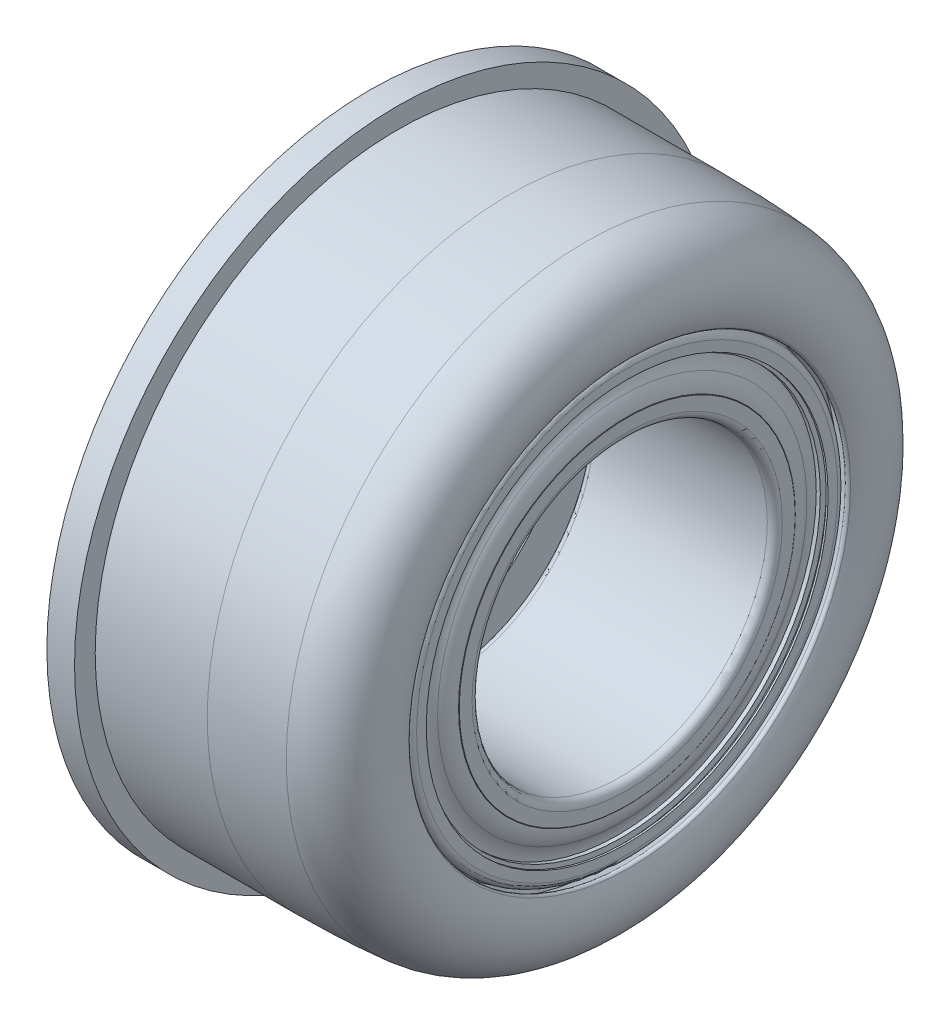
SolidWorks part; units mm, degrees
ref_plane "Front Plane" through (0, 0, 0) normal (0, 0, 1) x (1, 0, 0)
ref_plane "Top Plane" through (0, 0, 0) normal (0, 1, 0) x (1, 0, 0)
ref_plane "Right Plane" through (0, 0, 0) normal (1, 0, 0) x (0, 0, -1)
sketch "External Component" plane through (0, 0, 0) normal (0, 0, 1) x (1, 0, 0)
  line L0 (-3.6, 0) -> (3.6, 0) construction
  line L1 (-3.473, 4.25) -> (-2.723, 4.25) construction
  line L2 (-2.596, 4.377) -> (-2.596, 5.75) construction
  line L3 (3.6, 0) -> (3.6, 8.19) construction
  line L4 (-3.6, 4.377) -> (-3.473, 4.25) construction
  line L5 (1.03, 6.258) -> (1.4896, 7.0541) construction
  line L6 (-2.85, 8.19) -> (-2.85, 8.75) construction
  line L7 (-2.85, 8.75) -> (-3.6, 8.75) construction
  line L8 (-3.6, 8.75) -> (-3.6, 4.377) construction
  line L9 (2.13, 6.6433) -> (3.3318, 5.9494) construction
  line L10 (-2.723, 4.25) -> (-2.596, 4.377) construction
  line L11 (-2.596, 5.75) -> (-2.086, 5.75) construction
  line L12 (-2.086, 5.75) -> (-0.66, 6.1589) construction
  line L13 (-0.66, 6.1589) -> (-0.66, 6.258) construction
  line L14 (-0.66, 6.258) -> (1.03, 6.258) construction
  line L15 (2.13, 6.6433) -> (2.13, 7.4033) construction
  line L16 (2.13, 6.6433) -> (2.89, 6.6433) construction
  line L17 (0.185, 8.19) -> (-2.85, 8.19) construction
  arc A0 (3.4432, 5.9827) -> (2.2458, 8.1087) centre (2.13, 6.6433) ccw construction
  arc A1 (2.7882, 6.2633) -> (2.89, 6.6433) centre (2.13, 6.6433) ccw construction
  arc A2 (3.4432, 5.9827) -> (3.3318, 5.9494) centre (3.3718, 6.0187) cw construction
  arc A3 (2.89, 6.6433) -> (2.13, 7.4033) centre (2.13, 6.6433) ccw construction
  arc A4 (0.185, 8.19) -> (2.2458, 8.1087) centre (0.185, -17.9654) cw construction
  arc A5 (1.4896, 7.0541) -> (2.13, 7.4033) centre (2.0958, 6.7041) cw construction
  point P0 (-3.6, 4.25)
  point P3 (0, 0)
  point P19 (-2.596, 4.25)
  point P29 (0.185, 6.258)
  dimension "D10" = 0.08
  dimension "D11" = 0.76
  dimension "D5" = 0.7
  dimension "D1" = 0.254
  dimension "D2" = 1.5
  dimension "D6" = 0.51
  dimension "D7" = 164
  dimension "D8" = 0.508
  dimension "D9" = 30
  dimension "D13" = 2.94
  dimension "D14" = 1.69
  dimension "D15" = 120
sketch "Internal Component" plane through (0, 0, 0) normal (0, 0, 1) x (1, 0, 0)
  line L0 (3.1239, 5.4442) -> (2.9739, 5.4442)
  line L1 (3.374, 5.7058) -> (3.374, 5.4442)
  line L2 (3.374, 5.4442) -> (3.3232, 5.4442)
  line L3 (3.3232, 5.4442) -> (3.2334, 5.534)
  line L4 (3.2334, 5.534) -> (3.1239, 5.534)
  line L5 (3.1239, 5.534) -> (3.1239, 5.4442)
  line L6 (0.834, 4.2001) -> (0.834, 0) construction
  line L7 (-3.6, 0) -> (3.6, 0) construction
  line L8 (-1.706, 0) -> (3.374, 0) construction
  line L9 (2.9739, 5.4442) -> (2.9739, 5.1902)
  line L10 (-2.086, 5.75) -> (-0.66, 6.1589) construction
  line L11 (2.9739, 5.1902) -> (1.4226, 5.1902)
  line L12 (-1.306, 5.4442) -> (-1.306, 5.1902)
  line L13 (-1.456, 5.534) -> (-1.456, 5.4442)
  line L14 (-1.5654, 5.534) -> (-1.456, 5.534)
  line L15 (-1.6552, 5.4442) -> (-1.5654, 5.534)
  line L16 (-1.706, 5.4442) -> (-1.6552, 5.4442)
  line L17 (-1.706, 5.7058) -> (-1.706, 5.4442)
  line L18 (-1.456, 5.4442) -> (-1.306, 5.4442)
  line L19 (0.2454, 5.1902) -> (-1.306, 5.1902)
  line L20 (1.4226, 4.55) -> (3.1239, 4.55)
  line L22 (-1.706, 4.55) -> (-1.706, 4.2032)
  line L23 (-1.5028, 4) -> (3.1708, 4)
  line L24 (3.374, 4.55) -> (3.374, 4.2032)
  line L25 (3.1239, 4.55) -> (3.1239, 4.47)
  line L26 (3.1239, 4.47) -> (3.2334, 4.47)
  line L27 (3.2334, 4.47) -> (3.2334, 4.55)
  line L28 (3.2334, 4.55) -> (3.374, 4.55)
  line L29 (-1.5654, 4.55) -> (-1.706, 4.55)
  line L30 (-1.5654, 4.47) -> (-1.5654, 4.55)
  line L31 (-1.456, 4.47) -> (-1.5654, 4.47)
  line L32 (-1.456, 4.55) -> (-1.456, 4.47)
  line L33 (0.2454, 4.55) -> (-1.456, 4.55)
  line L34 (0.834, 4.8701) -> (0.164, 4.8701) construction
  line L35 (0.164, 5.1902) -> (0.164, 4.55) construction
  line L36 (-2.596, 4.377) -> (-2.596, 5.75) construction
  arc A0 (-1.5588, 5.9012) -> (3.2268, 5.9012) centre (0.834, -2.4435) cw
  arc A1 (3.2268, 5.9012) -> (3.374, 5.7058) centre (3.1708, 5.7058) cw
  arc A2 (-1.5588, 5.9012) -> (-1.706, 5.7058) centre (-1.5028, 5.7058) ccw
  arc A3 (1.4226, 5.1902) -> (0.2454, 5.1902) centre (0.834, 4.8701) ccw
  arc A4 (1.4226, 5.1902) -> (0.2454, 5.1902) centre (0.834, 4.8701) ccw construction
  arc A5 (0.2454, 4.55) -> (1.4226, 4.55) centre (0.834, 4.8701) ccw
  circle A6 centre (0.834, 4.8701) radius 0.67 construction
  arc A7 (3.374, 4.2032) -> (3.1708, 4) centre (3.1708, 4.2032) cw
  arc A8 (-1.5028, 4) -> (-1.706, 4.2032) centre (-1.5028, 4.2032) cw
  point P2 (3.3486, 5.4442)
  point P16 (0.834, 0)
  point P53 (0.164, 4.8701)
  dimension "D3" = 0.127
  dimension "D6" = 0.2032
  dimension "D12" = 0.2032
  dimension "D15" = 0.67
  dimension "D1" = 0.0508
  dimension "D2" = 135
  dimension "D5" = 5.08
  dimension "D7" = 0.254
  dimension "D8" = 0.15
  dimension "D9" = 0.4001
  dimension "D10" = 0.457
  dimension "D11" = 0.08
  dimension "D13" = 9.1
  dimension "D4" = 0.89
sketch "External Body Sketch" plane through (0, 0, 0) normal (0, 0, 1) x (1, 0, 0)
  line L0 (-2.85, 8.75) -> (-3.6, 8.75) construction
  line L1 (-2.85, 8.19) -> (-2.85, 8.75) construction
  line L2 (0.185, 8.19) -> (-2.85, 8.19) construction
  line L3 (2.13, 6.6433) -> (3.3318, 5.9494) construction
  line L4 (1.03, 6.258) -> (1.4896, 7.0541) construction
  line L5 (-0.66, 6.258) -> (1.03, 6.258) construction
  line L6 (-0.66, 6.1589) -> (-0.66, 6.258) construction
  line L7 (-2.086, 5.75) -> (-0.66, 6.1589) construction
  line L8 (-2.596, 5.75) -> (-2.086, 5.75) construction
  line L9 (-2.596, 4.377) -> (-2.596, 5.75) construction
  line L10 (-2.723, 4.25) -> (-2.596, 4.377) construction
  line L11 (-3.473, 4.25) -> (-2.723, 4.25) construction
  line L12 (-3.6, 4.377) -> (-3.473, 4.25) construction
  line L13 (-3.6, 8.75) -> (-3.6, 4.377) construction
  line L14 (-2.85, 8.75) -> (-3.6, 8.75)
  line L15 (-2.85, 8.19) -> (-2.85, 8.75)
  line L16 (0.185, 8.19) -> (-2.85, 8.19)
  line L17 (2.13, 6.6433) -> (3.3318, 5.9494)
  line L18 (1.03, 6.258) -> (1.4896, 7.0541)
  line L19 (-0.66, 6.258) -> (1.03, 6.258)
  line L20 (-0.66, 6.1589) -> (-0.66, 6.258)
  line L21 (-2.086, 5.75) -> (-0.66, 6.1589)
  line L22 (-2.596, 5.75) -> (-2.086, 5.75)
  line L23 (-2.596, 4.377) -> (-2.596, 5.75)
  line L24 (-2.723, 4.25) -> (-2.596, 4.377)
  line L25 (-3.473, 4.25) -> (-2.723, 4.25)
  line L26 (-3.6, 4.377) -> (-3.473, 4.25)
  line L27 (-3.6, 8.75) -> (-3.6, 4.377)
  arc A0 (2.2458, 8.1087) -> (0.185, 8.19) centre (0.185, -17.9654) ccw construction
  arc A1 (3.4432, 5.9827) -> (2.2458, 8.1087) centre (2.13, 6.6433) ccw construction
  arc A2 (3.3318, 5.9494) -> (3.4432, 5.9827) centre (3.3718, 6.0187) ccw construction
  arc A3 (2.7882, 6.2633) -> (2.89, 6.6433) centre (2.13, 6.6433) ccw construction
  arc A5 (2.2458, 8.1087) -> (0.185, 8.19) centre (0.185, -17.9654) ccw
  arc A6 (3.4432, 5.9827) -> (2.2458, 8.1087) centre (2.13, 6.6433) ccw
  arc A7 (3.3318, 5.9494) -> (3.4432, 5.9827) centre (3.3718, 6.0187) ccw
  arc A8 (2.7882, 6.2633) -> (2.89, 6.6433) centre (2.13, 6.6433) ccw
  arc A9 (2.89, 6.6433) -> (2.13, 7.4033) centre (2.13, 6.6433) ccw construction
  arc A10 (2.13, 7.4033) -> (1.4896, 7.0541) centre (2.0958, 6.7041) ccw construction
  arc A11 (2.89, 6.6433) -> (2.13, 7.4033) centre (2.13, 6.6433) ccw
  arc A12 (2.13, 7.4033) -> (1.4896, 7.0541) centre (2.0958, 6.7041) ccw
revolve "External Component Revolve" add sketch "External Body Sketch" angle 360 about L0 region at (-0.9112, 6.9559, 0)
sketch "Sketch6" plane through (0, 0, 0) normal (0, 0, 1) x (1, 0, 0)
  line L13 (-1.706, 4.55) -> (-1.706, 4.2032)
  line L14 (-1.5654, 4.55) -> (-1.706, 4.55)
  line L15 (-1.5654, 4.47) -> (-1.5654, 4.55)
  line L16 (-1.306, 5.1902) -> (0.2454, 5.1902)
  line L17 (-1.306, 5.4442) -> (-1.306, 5.1902)
  line L18 (-1.456, 5.4442) -> (-1.306, 5.4442)
  line L19 (-1.456, 5.534) -> (-1.456, 5.4442)
  line L20 (-1.5654, 5.534) -> (-1.456, 5.534)
  line L21 (-1.6552, 5.4442) -> (-1.5654, 5.534)
  line L22 (-1.706, 5.4442) -> (-1.6552, 5.4442)
  line L23 (-1.706, 5.7058) -> (-1.706, 5.4442)
  line L24 (3.374, 5.4442) -> (3.374, 5.7058)
  line L25 (3.3232, 5.4442) -> (3.374, 5.4442)
  line L26 (3.2334, 5.534) -> (3.3232, 5.4442)
  line L27 (3.1239, 5.534) -> (3.2334, 5.534)
  line L28 (3.1239, 5.4442) -> (3.1239, 5.534)
  line L29 (2.9739, 5.4442) -> (3.1239, 5.4442)
  line L30 (2.9739, 5.1902) -> (2.9739, 5.4442)
  line L31 (1.4226, 5.1902) -> (2.9739, 5.1902)
  line L32 (-1.306, 5.1902) -> (0.2454, 5.1902)
  line L33 (-1.306, 5.4442) -> (-1.306, 5.1902)
  line L34 (-1.456, 5.4442) -> (-1.306, 5.4442)
  line L35 (-1.456, 5.534) -> (-1.456, 5.4442)
  line L36 (-1.5654, 5.534) -> (-1.456, 5.534)
  line L37 (-1.6552, 5.4442) -> (-1.5654, 5.534)
  line L38 (-1.706, 5.4442) -> (-1.6552, 5.4442)
  line L39 (-1.706, 5.7058) -> (-1.706, 5.4442)
  line L40 (3.374, 5.4442) -> (3.374, 5.7058)
  line L41 (3.3232, 5.4442) -> (3.374, 5.4442)
  line L42 (3.2334, 5.534) -> (3.3232, 5.4442)
  line L43 (3.1239, 5.534) -> (3.2334, 5.534)
  line L44 (3.1239, 5.4442) -> (3.1239, 5.534)
  line L45 (2.9739, 5.4442) -> (3.1239, 5.4442)
  line L46 (2.9739, 5.1902) -> (2.9739, 5.4442)
  line L47 (1.4226, 5.1902) -> (2.9739, 5.1902)
  line L48 (-1.456, 4.47) -> (-1.5654, 4.47)
  line L49 (-1.456, 4.55) -> (-1.456, 4.47)
  line L50 (0.2454, 4.55) -> (-1.456, 4.55)
  line L51 (3.1239, 4.55) -> (1.4226, 4.55)
  line L52 (3.1239, 4.47) -> (3.1239, 4.55)
  line L53 (3.2334, 4.47) -> (3.1239, 4.47)
  line L54 (3.2334, 4.55) -> (3.2334, 4.47)
  line L55 (3.374, 4.55) -> (3.2334, 4.55)
  line L56 (3.374, 4.2032) -> (3.374, 4.55)
  line L57 (-1.5028, 4) -> (3.1708, 4)
  line L58 (-1.706, 4.55) -> (-1.706, 4.2032)
  line L59 (-1.5654, 4.55) -> (-1.706, 4.55)
  line L60 (-1.5654, 4.47) -> (-1.5654, 4.55)
  line L61 (-1.456, 4.47) -> (-1.5654, 4.47)
  line L62 (-1.456, 4.55) -> (-1.456, 4.47)
  line L63 (0.2454, 4.55) -> (-1.456, 4.55)
  line L64 (3.1239, 4.55) -> (1.4226, 4.55)
  line L65 (3.1239, 4.47) -> (3.1239, 4.55)
  line L66 (3.2334, 4.47) -> (3.1239, 4.47)
  line L67 (3.2334, 4.55) -> (3.2334, 4.47)
  line L68 (3.374, 4.55) -> (3.2334, 4.55)
  line L69 (3.374, 4.2032) -> (3.374, 4.55)
  line L70 (-1.5028, 4) -> (3.1708, 4)
  arc A3 (0.2454, 4.55) -> (1.4226, 4.55) centre (0.834, 4.8701) ccw
  arc A4 (1.4226, 5.1902) -> (0.2454, 5.1902) centre (0.834, 4.8701) ccw
  arc A5 (-1.5588, 5.9012) -> (-1.706, 5.7058) centre (-1.5028, 5.7058) ccw
  arc A6 (3.2268, 5.9012) -> (-1.5588, 5.9012) centre (0.834, -2.4435) ccw
  arc A7 (3.374, 5.7058) -> (3.2268, 5.9012) centre (3.1708, 5.7058) ccw
  arc A8 (1.4226, 5.1902) -> (0.2454, 5.1902) centre (0.834, 4.8701) ccw
  arc A9 (-1.5588, 5.9012) -> (-1.706, 5.7058) centre (-1.5028, 5.7058) ccw
  arc A10 (3.2268, 5.9012) -> (-1.5588, 5.9012) centre (0.834, -2.4435) ccw
  arc A11 (3.374, 5.7058) -> (3.2268, 5.9012) centre (3.1708, 5.7058) ccw
  arc A12 (3.1708, 4) -> (3.374, 4.2032) centre (3.1708, 4.2032) ccw
  arc A13 (-1.706, 4.2032) -> (-1.5028, 4) centre (-1.5028, 4.2032) ccw
  arc A14 (0.2454, 4.55) -> (1.4226, 4.55) centre (0.834, 4.8701) ccw
  arc A15 (3.1708, 4) -> (3.374, 4.2032) centre (3.1708, 4.2032) ccw
  arc A16 (-1.706, 4.2032) -> (-1.5028, 4) centre (-1.5028, 4.2032) ccw
  dimension "D1" = 0
  dimension "D2" = 0
revolve "Internal Component Revolve" add sketch "Sketch6" angle 360 about L0
sketch "O-Ring Sketch" plane through (0, 0, 0) normal (0, 0, 1) x (1, 0, 0)
  circle A2 centre (2.13, 6.6433) radius 0.76
  arc A3 (2.89, 6.6433) -> (2.13, 7.4033) centre (2.13, 6.6433) ccw construction
revolve "O-Ring" add sketch "O-Ring Sketch" angle 360 about L0
sketch "Sketch7" plane through (0, 0, 0) normal (0, 0, 1) x (1, 0, 0)
  line L1 (-0.309, 5.1749) -> (1.977, 5.1749)
  line L2 (-0.309, 5.1749) -> (-0.309, 4.5653)
  line L3 (-0.309, 4.5653) -> (1.977, 4.5653)
  line L4 (1.977, 5.1749) -> (1.977, 4.5653)
  line L5 (-0.309, 5.1749) -> (1.977, 4.5653) construction
  line L6 (1.977, 5.1749) -> (-0.309, 4.5653) construction
  dimension "D1" = 2.286
  dimension "D2" = 0.6096
revolve "Middle Ring" add sketch "Sketch7" angle 360 about L0
sketch "Sketch8" plane through (0, 0, 0) normal (0, 0, 1) x (1, 0, 0)
  line L0 (0.834, 5.5401) -> (0.834, 4.2001) construction
  line L1 (0.834, 5.5401) -> (0.834, 4.2001)
  circle A0 centre (0.834, 4.8701) radius 0.67 construction
  arc A1 (0.834, 4.2001) -> (0.834, 5.5401) centre (0.834, 4.8701) ccw
revolve "Rollerball" add sketch "Sketch8" angle 360 about L0
sketch "Sketch10" plane through (0, 0, 0) normal (0, 1, 0) x (1, 0, 0)
  line L0 (-3.6, 0) -> (3.6, 0) construction
  line L1 (0.834, 0.67) -> (-3.6, 0.67)
  line L2 (-3.6, 0.67) -> (-3.6, -0.67)
  line L3 (-3.6, -0.67) -> (0.834, -0.67)
  arc A0 (0.834, -0.67) -> (0.834, 0.67) centre (0.834, 0) ccw
  dimension "D1" = 0.67
extrude "Middle Ring Cut" cut sketch "Sketch10" along normal through all
pattern_circular "Cut Circle Pattern" count 10 over 360 about axis through (-3.6, 0, 0) along (-1, 0, 0) of "Middle Ring Cut" reverse direction yes
pattern_circular "Rollerball Cirlce Pattern" count 10 over 360 about axis through (-3.6, 0, 0) along (-1, 0, 0) of bodies 109
sketch "Sketch11" plane through (0, 0, 0) normal (0, 0, 1) x (1, 0, 0)
  line L0 (0.834, 0) -> (0.834, 4.2001) construction
  line L1 (3.1787, 5.534) -> (3.1787, 4.47) construction
  line L2 (3.2334, 5.534) -> (3.1239, 5.534) construction
  line L3 (3.1239, 4.47) -> (3.2334, 4.47) construction
  line L4 (3.1787, 5.002) -> (0.834, 5.002) construction
  line L5 (3.2334, 5.534) -> (3.2334, -5.534) construction
  line L6 (3.1239, 5.534) -> (3.2334, 5.534)
  line L7 (3.1239, 5.534) -> (3.1239, 5.374)
  line L8 (3.1239, 5.374) -> (3.2334, 5.374)
  line L9 (3.2334, 5.534) -> (3.2334, 5.374)
  line L10 (2.9854, 5.4315) -> (3.1124, 5.4315)
  line L11 (3.2402, 4.5627) -> (3.3672, 4.5627)
  line L12 (3.3037, 4.55) -> (3.3037, 4.5627) construction
  line L13 (3.2334, 4.55) -> (3.374, 4.55) construction
  line L14 (3.0489, 5.4315) -> (3.0489, 5.4442) construction
  line L15 (3.1239, 5.4442) -> (2.9739, 5.4442) construction
  line L16 (3.1129, 5.002) -> (3.2399, 5.002) construction
  line L17 (-3.6, 0) -> (3.6, 0) construction
  line L18 (-3.6, 0) -> (3.6, 0) construction
  line L19 (-1.456, 5.374) -> (-1.5654, 5.374)
  line L20 (-1.5654, 5.534) -> (-1.5654, 5.374)
  line L21 (-1.456, 5.534) -> (-1.5654, 5.534)
  line L22 (-1.456, 5.534) -> (-1.456, 5.374)
  line L23 (-1.3175, 5.4315) -> (-1.4445, 5.4315)
  line L24 (-1.5722, 4.5627) -> (-1.6992, 4.5627)
  line L25 (2.9854, 5.4315) -> (2.9854, 5.002) construction
  arc A0 (2.9854, 5.4315) -> (3.1129, 5.002) centre (3.773, 5.4315) ccw
  arc A1 (3.1124, 5.4315) -> (3.2399, 5.002) centre (3.9, 5.4315) ccw
  arc A2 (3.1129, 5.002) -> (3.2402, 4.5627) centre (2.4527, 4.5725) cw
  arc A3 (3.2399, 5.002) -> (3.3672, 4.5627) centre (2.5797, 4.5725) cw
  arc A4 (-1.4449, 5.002) -> (-1.5722, 4.5627) centre (-0.7847, 4.5725) ccw
  arc A5 (-1.3175, 5.4315) -> (-1.4449, 5.002) centre (-2.105, 5.4315) cw
  arc A6 (-1.4445, 5.4315) -> (-1.5719, 5.002) centre (-2.232, 5.4315) cw
  arc A7 (-1.5719, 5.002) -> (-1.6992, 4.5627) centre (-0.9117, 4.5725) ccw
  dimension "D2" = 0.127
  dimension "D1" = 0.16
  dimension "D3" = 0.0127
revolve "Shielded" add sketch "Sketch11" angle 360 about L18
sketch "Sketch12" plane through (0, 0, 0) normal (0, 0, 1) x (1, 0, 0)
  line L0 (0.834, 4.2001) -> (0.834, 0) construction
  line L1 (-3.6, 0) -> (3.6, 0) construction
  line L2 (3.1787, 5.534) -> (3.1787, 4.47) construction
  line L3 (3.2334, 5.534) -> (3.1239, 5.534) construction
  line L4 (3.1239, 4.47) -> (3.2334, 4.47) construction
  line L5 (3.1787, 5.002) -> (0.834, 5.002) construction
  line L6 (3.1342, 5.5276) -> (3.2231, 5.5276)
  line L7 (3.2231, 5.5276) -> (3.2231, 5.4807)
  line L8 (3.2231, 5.4807) -> (3.374, 5.3298)
  line L9 (3.374, -5.4442) -> (3.374, 5.4442) construction
  line L10 (3.374, 5.3298) -> (3.374, 4.6742)
  line L11 (3.3232, 5.4442) -> (3.2334, 5.534) construction
  line L12 (3.1342, 5.5276) -> (3.1342, 5.4006)
  line L13 (3.1342, 5.4006) -> (3.2851, 5.2497)
  line L14 (3.2851, 5.2497) -> (3.2851, 4.7542)
  line L16 (3.1342, 5.4006) -> (3.2231, 5.4807) construction
  line L17 (3.2851, 5.002) -> (3.374, 5.002) construction
  line L18 (3.1342, 4.4764) -> (3.1342, 4.6034)
  line L19 (3.1342, 4.4764) -> (3.2231, 4.4764)
  line L20 (3.2231, 4.4764) -> (3.2231, 4.5233)
  line L21 (3.2231, 4.5233) -> (3.374, 4.6742)
  line L22 (3.1342, 4.6034) -> (3.2851, 4.7542)
  line L23 (-1.4662, 4.4764) -> (-1.5551, 4.4764)
  line L24 (-1.5551, 4.4764) -> (-1.5551, 4.5233)
  line L25 (-1.5551, 4.5233) -> (-1.706, 4.6742)
  line L26 (-1.706, 5.3298) -> (-1.706, 4.6742)
  line L27 (-1.5551, 5.4807) -> (-1.706, 5.3298)
  line L28 (-1.5551, 5.5276) -> (-1.5551, 5.4807)
  line L29 (-1.4662, 5.5276) -> (-1.5551, 5.5276)
  line L30 (-1.4662, 5.5276) -> (-1.4662, 5.4006)
  line L31 (-1.4662, 5.4006) -> (-1.6171, 5.2497)
  line L32 (-1.6171, 5.2497) -> (-1.6171, 4.7542)
  line L33 (-1.4662, 4.6034) -> (-1.6171, 4.7542)
  line L34 (-1.4662, 4.4764) -> (-1.4662, 4.6034)
  point P19 (3.1787, 5.5276)
  dimension "D1" = 0.0064
  dimension "D2" = 48
  dimension "D3" = 0.127
  dimension "D4" = 0.0889
revolve "Sealed" [suppressed] add sketch "Sketch12" angle 360 about L1
ref_axis "Center Axis 1" through (3.1708, 0, 0) along (-1, 0, 0)
ref_plane "Contact Plane 1" through (-3.6, 0, 0) normal (-1, 0, 0) x (0, 0, 1)
equation "\"D1@Rollerball Cirlce Pattern\" = \"Instance No@Cut Circle Pattern\""
equation "\"Lip Length@External Component\" = IIF ( \"Flange OD@External Component\" < 25 , 4.5 , 6.6 )"
equation "\"D13@External Component\"=IIF ( \"Flange OD@External Component\" < 25 , 2.94 , 4 )"
equation "\"D14@External Component\"=IIF ( \"Flange OD@External Component\" < 25 , 1.69 , 3.25 )"
equation "\"D1@External Component\" = IIF ( \"Flange OD@External Component\" < 25 , 0.254 , 0.508 )"
equation "\"D8@External Component\" = IIF ( \"Flange OD@External Component\" < 25 , .508 , 0.762 )"
equation "\"D2@External Component\" = IIF ( \"Flange OD@External Component\" < 25 , 1.5 , 3.3 )"
equation "\"D5@Internal Component\" = IIF ( \"Flange OD@External Component\" < 25 , 5.08 , 6.985 )"
equation "\"D13@Internal Component\"=IIF ( \"ID@Internal Component\" < 9.5 , 9.1 , 12.7 )"
equation "\"D10@Internal Component\" = IIF ( \"Flange OD@External Component\" < 25 , .457 , .762 )"
equation "\"D15@Internal Component\" = IIF ( \"Flange OD@External Component\" < 25 , .67 , 1.2 )"
equation "\"D1@Sketch7\" = IIF ( \"Flange OD@External Component\" < 25 , 2.286 , 3.05 )"
equation "\"D1@Sketch10\"=\"D15@Internal Component\""
